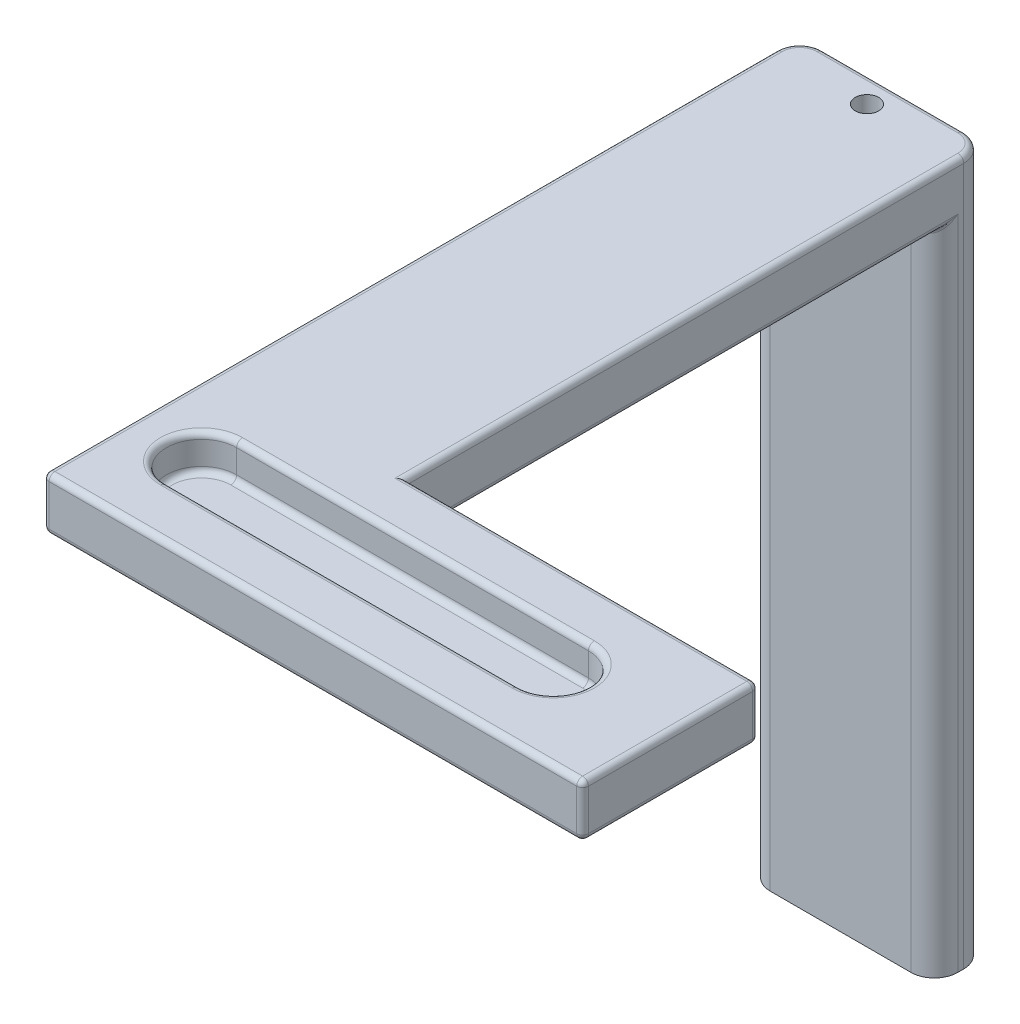
SolidWorks part; units mm, degrees
ref_plane "Front Plane" through (0, 0, 0) normal (0, 0, 1) x (1, 0, 0)
ref_plane "Top Plane" through (0, 0, 0) normal (0, 1, 0) x (1, 0, 0)
ref_plane "Right Plane" through (0, 0, 0) normal (1, 0, 0) x (0, 0, -1)
sketch "Sketch1" plane through (0, 0, 0) normal (0, 1, 0) x (1, 0, 0)
  line L1 (8, -2.25) -> (-8, -2.25)
  line L2 (8, -2.25) -> (8, 2.25)
  line L3 (8, 2.25) -> (-8, 2.25)
  line L4 (-8, -2.25) -> (-8, 2.25)
  line L5 (8, -2.25) -> (-8, 2.25) construction
  line L6 (8, 2.25) -> (-8, -2.25) construction
  point P0 (0, 0)
  dimension "D1" = 4.5
  dimension "D2" = 16
extrude "Boss-Extrude1" add sketch "Sketch1" along normal blind 60
sketch "Sketch2" plane through (0, 0, 2.25) normal (0, 0, 1) x (1, 0, 0)
  line L0 (0, 0) -> (0, 60) construction
  line L1 (-8, 60) -> (8, 60) construction
  line L2 (-8, 55.5) -> (-8, 60)
  line L3 (-8, 55.5) -> (8, 55.5)
  line L4 (-8, 60) -> (8, 60)
  line L5 (8, 55.5) -> (8, 60)
  line L6 (-8, 55.5) -> (8, 60) construction
  line L7 (-8, 60) -> (8, 55.5) construction
  point P6 (0, 57.75)
  dimension "D1" = 4.5
extrude "Boss-Extrude2" add sketch "Sketch2" along normal blind 60
sketch "Sketch3" plane through (8, 0, 0) normal (1, 0, 0) x (0, 0, -1)
  line L0 (-62.25, 55.5) -> (-2.25, 55.5) construction
  line L1 (-62.25, 60) -> (-47.25, 60)
  line L2 (-62.25, 60) -> (-62.25, 55.5)
  line L3 (-62.25, 55.5) -> (-47.25, 55.5)
  line L4 (-47.25, 60) -> (-47.25, 55.5)
  dimension "D1" = 15
extrude "Boss-Extrude3" add sketch "Sketch3" along normal blind 30
sketch "Sketch4" plane through (0, 60, 0) normal (0, 1, 0) x (1, 0, 0)
  line L0 (38, -54.75) -> (-8, -54.75) construction
  line L1 (38, -47.25) -> (38, -62.25) construction
  line L2 (-8, 2.25) -> (-8, -62.25) construction
  line L3 (28, -54.75) -> (-2, -54.75) construction
  line L4 (28, -57.75) -> (-2, -57.75)
  line L5 (28, -51.75) -> (-2, -51.75)
  arc A0 (28, -57.75) -> (28, -51.75) centre (28, -54.75) ccw
  arc A1 (-2, -51.75) -> (-2, -57.75) centre (-2, -54.75) ccw
  point P8 (13, -54.75)
  dimension "D1" = 30
  dimension "D2" = 6
  dimension "D3" = 10
extrude "Cut-Extrude1" cut sketch "Sketch4" against normal blind 3
sketch "Sketch5" plane through (0, 55.5, 0) normal (0, -1, 0) x (1, 0, 0)
  line L0 (38, 54.75) -> (-8, 54.75) construction
  line L1 (38, 62.25) -> (38, 47.25) construction
  line L2 (-8, 62.25) -> (-8, 2.25) construction
  line L3 (38, 51) -> (-8, 51) construction
  line L4 (38, 58.5) -> (-8, 58.5) construction
  line L5 (32, 51) -> (-2, 51) construction
  line L6 (32, 49.25) -> (-2, 49.25)
  line L7 (32, 52.75) -> (-2, 52.75)
  line L8 (32, 58.5) -> (-2, 58.5) construction
  line L9 (32, 56.75) -> (-2, 56.75)
  line L10 (32, 60.25) -> (-2, 60.25)
  arc A0 (32, 49.25) -> (32, 52.75) centre (32, 51) ccw
  arc A1 (-2, 52.75) -> (-2, 49.25) centre (-2, 51) ccw
  arc A2 (32, 56.75) -> (32, 60.25) centre (32, 58.5) ccw
  arc A3 (-2, 60.25) -> (-2, 56.75) centre (-2, 58.5) ccw
  point P13 (15, 51)
  point P20 (15, 58.5)
  dimension "D1" = 3.75
  dimension "D2" = 3.75
  dimension "D3" = 3.5
  dimension "D4" = 3.5
  dimension "D5" = 6
  dimension "D6" = 6
  dimension "D7" = 6
  dimension "D8" = 6
extrude "Boss-Extrude4" add sketch "Sketch5" along normal blind 2
fillet "Fillet1" radius 2 4 edges at (8, 30, -2.25) (-8, 30, -2.25) (8, 27.75, 2.25) (-8, 27.75, 2.25)
fillet "Fillet2" radius 0.5 16 edges at (8, 60, 23.5) (7.4142, 60, -1.6642) (0, 60, -2.25) (-7.4142, 60, -1.6642) (23, 55.5, 47.25) (38, 55.5, 54.75) (38, 60, 54.75) (23, 60, 47.25) (15, 55.5, 62.25) (15, 60, 62.25) (8, 55.5, 23.75) (-8, 55.5, 31.25) (-8, 60, 31) (-8, 57.75, 62.25) (38, 57.75, 47.25) (38, 57.75, 62.25)
fillet "Fillet3" radius 0.5 8 edges at (13, 60, 51.75) (-5, 60, 54.75) (13, 60, 57.75) (31, 60, 54.75) (13, 57, 57.75) (-5, 57, 54.75) (13, 57, 51.75) (31, 57, 54.75)
fillet "Fillet4" radius 0.5 21 edges at (-7.7247, 55.5534, 1.2626) (7.7247, 55.5534, 1.2626) (15, 55.5, 60.25) (-3.75, 55.5, 58.5) (15, 55.5, 56.75) (33.75, 55.5, 58.5) (0, 55.5, 2.25) (-6.8229, 55.5, 2.0729) (6.8229, 55.5, 2.0729) (15, 55.5, 52.75) (-3.75, 55.5, 51) (15, 55.5, 49.25) (33.75, 55.5, 51) (15, 53.5, 56.75) (-3.75, 53.5, 58.5) (15, 53.5, 60.25) (33.75, 53.5, 58.5) (15, 53.5, 49.25) (-3.75, 53.5, 51) (15, 53.5, 52.75) (33.75, 53.5, 51)
sketch "Sketch6" plane through (0, 60, 0) normal (0, 1, 0) x (1, 0, 0)
  circle A0 centre (0, 0) radius 1
  dimension "D1" = 2
extrude "Cut-Extrude2" cut sketch "Sketch6" against normal blind 30
